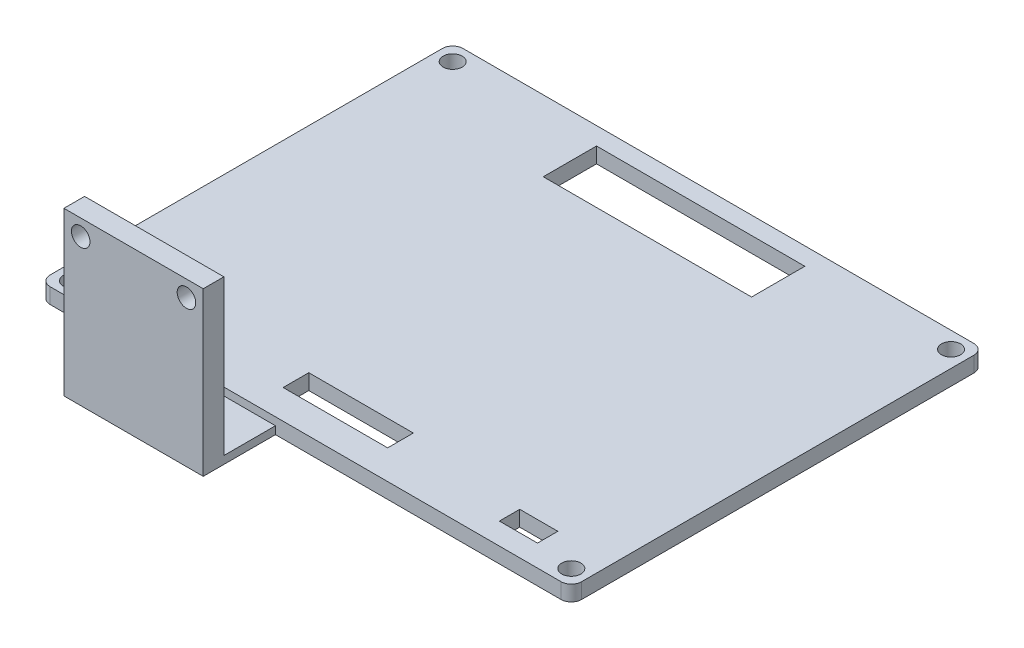
SolidWorks part; units mm, degrees
ref_plane "前视基准面" through (0, 0, 0) normal (0, 0, 1) x (1, 0, 0)
ref_plane "上视基准面" through (0, 0, 0) normal (0, 1, 0) x (1, 0, 0)
ref_plane "右视基准面" through (0, 0, 0) normal (1, 0, 0) x (0, 0, -1)
sketch "草图1" plane through (0, 0, 0) normal (0, 1, 0) x (1, 0, 0)
  line L0 (-51.5, 40) -> (-48.2968, 36.7968) construction
  line L1 (49.5, -40) -> (-49.5, -40)
  line L2 (51.5, -38) -> (51.5, 38)
  line L3 (49.5, 40) -> (-49.5, 40)
  line L4 (-51.5, -38) -> (-51.5, 38)
  line L5 (51.5, -40) -> (-51.5, 40) construction
  line L6 (51.5, 40) -> (-51.5, -40) construction
  line L7 (20.1874, 26.2491) -> (-20.1874, 26.2491)
  line L8 (20.1874, 26.2491) -> (20.1874, 36.5704)
  line L9 (20.1874, 36.5704) -> (-20.1874, 36.5704)
  line L10 (-20.1874, 26.2491) -> (-20.1874, 36.5704)
  line L11 (20.1874, 26.2491) -> (-20.1874, 36.5704) construction
  line L12 (20.1874, 36.5704) -> (-20.1874, 26.2491) construction
  line L13 (0, 31.4098) -> (0, -40) construction
  line L14 (51.5, 0) -> (-51.5, 0)
  line L15 (33.3536, -35.8039) -> (40.7411, -35.8039)
  line L16 (-10.0207, -29.3673) -> (10.2401, -29.3673)
  line L17 (-10.0207, -29.3673) -> (-10.0207, -34.3411)
  line L18 (-10.0207, -34.3411) -> (10.2401, -34.3411)
  line L19 (10.2401, -29.3673) -> (10.2401, -34.3411)
  line L20 (-33.3536, -31.8542) -> (-40.7411, -31.8542)
  line L21 (-33.3536, -31.8542) -> (-33.3536, -35.8039)
  line L22 (-33.3536, -35.8039) -> (-40.7411, -35.8039)
  line L23 (-40.7411, -31.8542) -> (-40.7411, -35.8039)
  line L24 (40.7411, -31.8542) -> (40.7411, -35.8039)
  line L25 (33.3536, -31.8542) -> (40.7411, -31.8542)
  line L26 (33.3536, -31.8542) -> (33.3536, -35.8039)
  circle A0 centre (-48.2968, 36.7968) radius 1.85
  circle A1 centre (48.2968, 36.7968) radius 1.85
  circle A2 centre (48.2968, -36.7968) radius 1.85
  circle A3 centre (-48.2968, -36.7968) radius 1.85
  arc A4 (-49.5, -40) -> (-51.5, -38) centre (-49.5, -38) cw
  arc A5 (49.5, -40) -> (51.5, -38) centre (49.5, -38) ccw
  arc A6 (51.5, 38) -> (49.5, 40) centre (49.5, 38) ccw
  arc A7 (-49.5, 40) -> (-51.5, 38) centre (-49.5, 38) ccw
  point P0 (0, 0)
  point P6 (0, 31.4098)
  point P18 (0, 0)
  dimension "D4" = 2
  dimension "D1" = 103
  dimension "D3" = 45
extrude "凸台-拉伸1" add sketch "草图1" along normal blind 3 contours L3 A7 L4 L14 L2 A6 L7 L10 L9 L8 A0 A1 | L1 A5 L2 L14 L4 A4 A3 A2 region at (-0.0028, 0, 19.3914) region at (0, 0, -18.6007)
ref_plane "基准面1" through (0, 0, 40) normal (0, 0, 1) x (1, 0, 0)
sketch "草图2" plane through (0, 0, 40) normal (0, 0, 1) x (1, 0, 0)
  line L6 (49.5, 0) -> (-49.5, 0) construction
  line L7 (-32.8465, 1.5) -> (-5.8465, 1.5)
  line L8 (-32.8465, 1.5) -> (-32.8465, 0)
  line L9 (-32.8465, 0) -> (-5.8465, 0)
  line L10 (-5.8465, 1.5) -> (-5.8465, 0)
extrude "凸台-拉伸2" add sketch "草图2" along normal blind 14 contours L8 L7 L10 L9
sketch "草图4" plane through (0, 1.5, 0) normal (0, 1, 0) x (1, 0, 0)
  line L0 (-19.3465, -54) -> (-19.3465, -50) construction
  line L5 (-32.8465, -54) -> (-5.8465, -54) construction
  line L6 (-32.8465, -54) -> (-32.8465, -40) construction
  line L17 (-5.8465, -54) -> (-32.8465, -54)
  line L18 (-5.8465, -54) -> (-5.8465, -50)
  line L19 (-5.8465, -50) -> (-32.8465, -50)
  line L20 (-32.8465, -54) -> (-32.8465, -50)
  line L21 (-5.8465, -54) -> (-32.8465, -50) construction
  line L22 (-5.8465, -50) -> (-32.8465, -54) construction
  point P4 (-19.3465, -52)
  point P5 (-32.8465, -54)
  point P6 (-34.1089, -48.6371)
  point P15 (0, 0)
  dimension "D1" = 4
extrude "凸台-拉伸3" add sketch "草图4" along normal blind 30 contours L18 L17 L20 L19
sketch "草图5" plane through (0, 0, 54) normal (0, 0, 1) x (1, 0, 0)
  line L2 (-5.8465, 31.5) -> (-32.8465, 31.5) construction
  line L3 (-19.3465, 31.5) -> (-19.3465, 3.1595) construction
  circle A1 centre (-29.5965, 28.3813) radius 1.8
  circle A2 centre (-9.0965, 28.3813) radius 1.8
  dimension "D1" = 20.5
extrude "切除-拉伸1" cut sketch "草图5" against normal blind 30 contours A1 | A2
